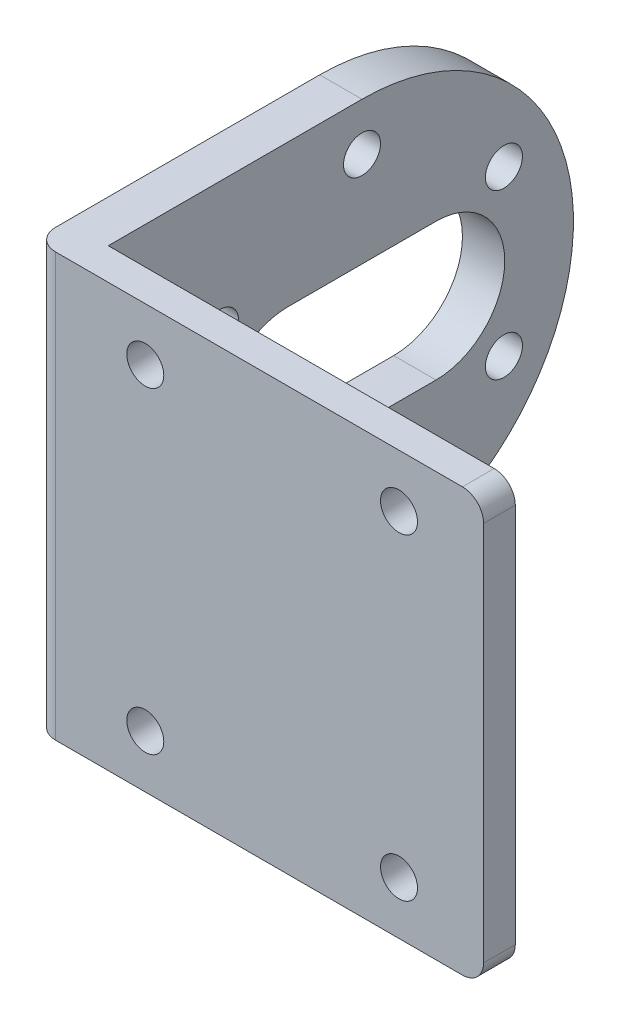
SolidWorks part; units mm, degrees
ref_plane "Front Plane" through (0, 0, 0) normal (0, 0, 1) x (1, 0, 0)
ref_plane "Top Plane" through (0, 0, 0) normal (0, 1, 0) x (1, 0, 0)
ref_plane "Right Plane" through (0, 0, 0) normal (1, 0, 0) x (0, 0, -1)
sketch "Sketch1" plane through (0, 0, 0) normal (0, 1, 0) x (1, 0, 0)
  line L0 (0, 0) -> (0, 27)
  line L1 (0, 27) -> (3, 27)
  line L2 (3, 27) -> (3, 3)
  line L3 (3, 3) -> (42.5, 3)
  line L4 (42.5, 3) -> (42.5, 0)
  line L5 (42.5, 0) -> (0, 0)
  dimension "D1" = 27
  dimension "D2" = 3
  dimension "D3" = 3
  dimension "D4" = 42.5
extrude "Boss-Extrude1" add sketch "Sketch1" along normal blind 40
sketch "Sketch2" plane through (3, 0, 0) normal (1, 0, 0) x (0, 0, -1)
  line L4 (3, 0) -> (27, 0) construction
  line L5 (3, 40) -> (27, 40) construction
  line L11 (3, 0) -> (27, 0)
  line L12 (27, 0) -> (27, 40)
  line L13 (27, 40) -> (3, 40)
  line L14 (3, 40) -> (3, 0)
  line L15 (3, 0) -> (27, 0)
  line L17 (27, 40) -> (3, 40)
  line L18 (3, 40) -> (3, 0)
  arc A0 (27, 40) -> (27, 0) centre (27, 20) cw
  dimension "D1" = 0
extrude "Boss-Extrude2" add sketch "Sketch2" along normal blind 1 and the other way blind 3
sketch "Sketch3" plane through (4, 0, 0) normal (1, 0, 0) x (0, 0, -1)
  line L0 (27, 40) -> (3, 40) construction
  line L1 (20, 26.5) -> (34, 26.5)
  line L3 (20, 13.5) -> (34, 13.5)
  line L5 (20, 26.5) -> (27, 20) construction
  line L6 (27, 20) -> (34, 26.5) construction
  arc A0 (34, 26.5) -> (34, 13.5) centre (34, 20) cw
  arc A1 (20, 26.5) -> (20, 13.5) centre (20, 20) ccw
  point P0 (27, 20)
  dimension "D1" = 14
  dimension "D2" = 13
  dimension "D3" = 13.5
extrude "Cut-Extrude1" cut sketch "Sketch3" against normal through all
sketch "Sketch4" plane through (4, 0, 0) normal (1, 0, 0) x (0, 0, -1)
  line L0 (0, 40) -> (0, 0) construction
  circle A0 centre (27, 20) radius 15.5 construction
  dimension "D1" = 31
  dimension "D2" = 27
sketch "Sketch5" plane through (4, 0, 0) normal (1, 0, 0) x (0, 0, -1)
  circle A2 centre (27, 4.5) radius 1.75
  circle A3 centre (27, 20) radius 15.5 construction
  circle A4 centre (13.5766, 12.25) radius 1.75
  circle A5 centre (13.5766, 27.75) radius 1.75
  circle A6 centre (27, 35.5) radius 1.75
  circle A7 centre (40.4234, 27.75) radius 1.75
  circle A8 centre (40.4234, 12.25) radius 1.75
  point P17 (27, 20)
  dimension "D1" = 3.5
  dimension "D2" = 6
extrude "Cut-Extrude2" cut sketch "Sketch5" against normal through all
fillet "Fillet1" radius 2 3 edges at (42.5, 40, -1.5) (42.5, 0, -1.5) (0, 20, 0)
sketch "Sketch6" plane through (0, 0, 0) normal (0, 0, 1) x (1, 0, 0)
  line L0 (42.5, 38) -> (42.5, 2) construction
  line L1 (2, 0) -> (40.5, 0) construction
  circle A0 centre (34.5, 5) radius 1.75
  circle A1 centre (34.5, 35) radius 1.75
  circle A2 centre (10.5, 35) radius 1.75
  circle A3 centre (10.5, 5) radius 1.75
  dimension "D1" = 3.5
  dimension "D2" = 8
  dimension "D3" = 5
  dimension "D5" = 30
  dimension "D6" = 24
  dimension "D4" = 2
extrude "Cut-Extrude3" cut sketch "Sketch6" against normal up to next
